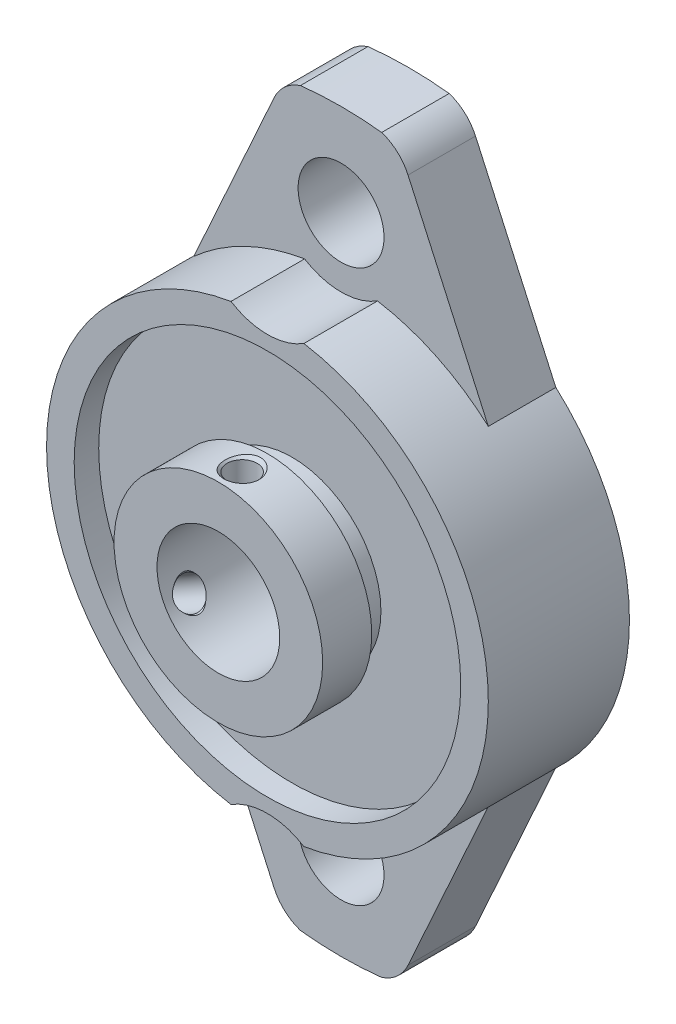
SolidWorks part; units mm, degrees
material "普通碳钢"
ref_plane "前视基准面" through (0, 0, 0) normal (0, 0, 1) x (1, 0, 0)
ref_plane "上视基准面" through (0, 0, 0) normal (0, 1, 0) x (1, 0, 0)
ref_plane "右视基准面" through (0, 0, 0) normal (1, 0, 0) x (0, 0, -1)
sketch "草图1" plane through (0, 0, 0) normal (1, 0, 0) x (0, 0, -1)
  line L0 (-7.75, 8.5) -> (-7.75, 5)
  line L1 (-7.75, 5) -> (6.25, 5)
  line L2 (6.25, 5) -> (6.25, 7.2)
  line L3 (6.25, 7.3) -> (6.25, 15.75)
  line L4 (6.25, 15.75) -> (7.75, 15.75)
  line L5 (7.75, 15.75) -> (7.75, 30)
  line L6 (7.75, 30) -> (2.25, 30)
  line L7 (2.25, 30) -> (2.25, 18)
  line L8 (2.25, 18) -> (-3.75, 18)
  line L9 (-3.75, 18) -> (-3.75, 15.75)
  line L10 (-3.75, 15.75) -> (-1.75, 15.75)
  line L11 (-1.75, 15.75) -> (-1.75, 7.25)
  line L12 (-1.75, 7.25) -> (-3.75, 7.25)
  line L13 (-3.75, 7.25) -> (-3.75, 8.5)
  line L14 (-3.75, 8.5) -> (-7.75, 8.5)
  line L15 (7.75, 0) -> (-7.75, 0) construction
  arc A0 (6.25, 7.2) -> (6.25, 7.3) centre (6.25, 7.25) cw
revolve "旋转1" add sketch "草图1" angle 360 about L15 reverse direction yes
sketch "草图2" plane through (0, 0, 0) normal (0, 0, 1) x (1, 0, 0)
  line L0 (-72, -120) -> (72, -120)
  line L1 (72, -120) -> (72, 120)
  line L2 (72, 120) -> (-72, 120)
  line L3 (-72, 120) -> (-72, -120)
  line L4 (-12, -13.4164) -> (-5.4572, -27.8835)
  line L5 (-2.1771, -30) -> (2.1771, -30)
  line L6 (5.4572, -27.8835) -> (12, -13.4164)
  line L7 (12, 13.4164) -> (5.4572, 27.8835)
  line L8 (2.1771, 30) -> (-2.1771, 30)
  line L9 (-5.4572, 27.8835) -> (-12, 13.4164)
  arc A0 (-12, 13.4164) -> (-12, -13.4164) centre (0, 0) ccw
  arc A1 (-5.4572, -27.8835) -> (-2.1771, -30) centre (-2.1771, -26.4) ccw
  arc A2 (2.1771, -30) -> (5.4572, -27.8835) centre (2.1771, -26.4) ccw
  arc A3 (12, -13.4164) -> (12, 13.4164) centre (0, 0) ccw
  arc A4 (5.4572, 27.8835) -> (2.1771, 30) centre (2.1771, 26.4) ccw
  arc A5 (-2.1771, 30) -> (-5.4572, 27.8835) centre (-2.1771, 26.4) ccw
extrude "切除-拉伸1" cut sketch "草图2" along normal blind 15.5 and the other way blind 15.5
sketch "草图3" plane through (0, 0, 0) normal (1, 0, 0) x (0, 0, -1)
  line L0 (-7.75, 22.5) -> (-7.75, 28.1)
  line L1 (-7.75, 28.1) -> (2.25, 28.1)
  line L2 (2.25, 28.1) -> (2.25, 26)
  line L3 (2.25, 26) -> (7.75, 26)
  line L4 (7.75, 26) -> (7.75, 22.5)
  line L5 (7.75, 22.5) -> (-7.75, 22.5)
  line L6 (7.75, 22.5) -> (-7.75, 22.5) construction
revolve "切除-旋转1" cut sketch "草图3" angle 360 about L6 reverse direction yes
sketch "草图4" plane through (0, 0, 0) normal (1, 0, 0) x (0, 0, -1)
  line L0 (-7.75, -22.5) -> (-7.75, -16.9)
  line L1 (-7.75, -16.9) -> (2.25, -16.9)
  line L2 (2.25, -16.9) -> (2.25, -19)
  line L3 (2.25, -19) -> (7.75, -19)
  line L4 (7.75, -19) -> (7.75, -22.5)
  line L5 (7.75, -22.5) -> (-7.75, -22.5)
  line L6 (7.75, -22.5) -> (-7.75, -22.5) construction
revolve "切除-旋转2" cut sketch "草图4" angle 360 about L6 reverse direction yes
sketch "草图5" plane through (0, 0, 0) normal (1, 0, 0) x (0, 0, -1)
  line L0 (-5.8125, 8.5) -> (-4.3125, 8.5)
  line L1 (-4.3125, 8.5) -> (-4.583, 8.2295)
  line L2 (-4.583, 8.2295) -> (-4.583, 4.9205)
  line L3 (-4.583, 4.9205) -> (-4.3125, 4.65)
  line L4 (-4.3125, 4.65) -> (-5.8125, 4.65)
  line L5 (-5.8125, 4.65) -> (-5.8125, 8.5)
  line L6 (-5.8125, 4.65) -> (-5.8125, 8.5) construction
revolve "切除-旋转3" cut sketch "草图5" angle 360 about L6 reverse direction yes
cosmetic thread "装饰螺纹线1" parameters "D1"=3.5795, "D2"=3
ref_plane "基准面1" through (0, 0, 5.8125) normal (0, 0, 1) x (1, 0, 0)
sketch "草图6" plane through (0, 0, 5.8125) normal (0, 0, 1) x (1, 0, 0)
  line L0 (-4.027, -2.325) -> (-3.277, -3.624)
  line L1 (-3.277, -3.624) -> (-3.6465, -3.525)
  line L2 (-3.6465, -3.525) -> (-6.5122, -5.1795)
  line L3 (-6.5122, -5.1795) -> (-6.6112, -5.549)
  line L4 (-6.6112, -5.549) -> (-7.3612, -4.25)
  line L5 (-7.3612, -4.25) -> (-4.027, -2.325)
  line L6 (-7.3612, -4.25) -> (-4.027, -2.325) construction
revolve "切除-旋转4" cut sketch "草图6" angle 360 about L6 reverse direction yes
cosmetic thread "装饰螺纹线2" parameters "D1"=3.5795, "D2"=3
ref_plane "基准面2" through (0, 0, 0) normal (0.7071, 0.7071, 0) x (0.7071, -0.7071, 0)
ref_plane "基准面3" through (-3.5355, -3.5355, 0) normal (0.7071, 0.7071, 0) x (0.7071, -0.7071, 0)
ref_plane "基准面4" through (0, 5, 0) normal (0, 1, 0) x (1, 0, 0)
ref_plane "基准面5" through (0, 0, 0) normal (0.866, 0.5, 0) x (0, 0, -1)
ref_plane "基准面6" through (-4.3301, -2.5, 0) normal (0.866, 0.5, 0) x (0, 0, -1)
ref_plane "to_screw XY" through (0, 5, 0) normal (0, 1, 0) x (1, 0, 0)
ref_plane "to_screw XZ" through (0, 0, 5.8125) normal (0, 0, 1) x (1, 0, 0)
ref_plane "to_screw YZ" through (0, 0, 0) normal (1, 0, 0) x (0, 0, -1)
ref_axis "to_screw X" through (-80.9, 5, 5.8125) along (1, 0, 0)
ref_axis "to_screw Y" through (0, 5, 50) along (0, 0, -1)
ref_axis "to_screw Z" through (0, 50, 5.8125) along (0, -1, 0)
sketch3d "to_screw"
  point P0 (0, 5, 5.8125)
ref_plane "to_screw_1 XY" through (-4.3301, -2.5, 0) normal (-0.866, -0.5, 0) x (0, 0, 1)
ref_plane "to_screw_1 XZ" through (0, 0, 5.8125) normal (0, 0, -1) x (-1, 0, 0)
ref_plane "to_screw_1 YZ" through (0, 0, 0) normal (0.5, -0.866, 0) x (-0.866, -0.5, 0)
ref_axis "to_screw_1 X" through (-29.3301, 40.8013, 5.8125) along (0.5, -0.866, 0)
ref_axis "to_screw_1 Y" through (-4.3301, -2.5, -80.9) along (0, 0, 1)
ref_axis "to_screw_1 Z" through (-70.0615, -40.45, 5.8125) along (0.866, 0.5, 0)
sketch3d "to_screw_1"
  point P0 (-4.3301, -2.5, 5.8125)
